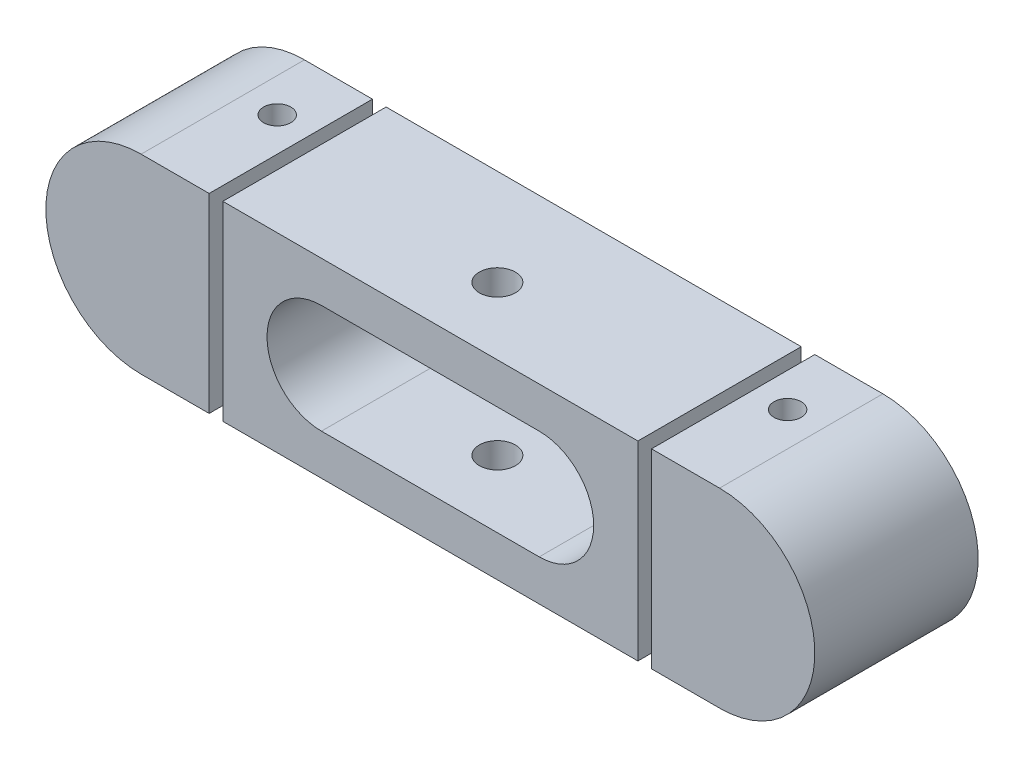
SolidWorks part; units mm, degrees
note: The reader was unsure of these and kept them because the rebuilt part matched: shared geometry of "草图2<3>".
ref_plane "前视基准面" through (0, 0, 0) normal (0, 0, 1) x (1, 0, 0)
ref_plane "上视基准面" through (0, 0, 0) normal (0, 1, 0) x (1, 0, 0)
ref_plane "右视基准面" through (0, 0, 0) normal (1, 0, 0) x (0, 0, -1)
other "Configuration Table"
sketch "草图2" plane through (0, 0, 0) normal (0, 0, 1) x (1, 0, 0)
  line L0 (-42.5, 36.6111) -> (-42.5, -23.6839) construction
  line L6 (-26.5, 0) -> (-58.5, 0) construction
  line L7 (-26.5, -8) -> (-58.5, -8)
  line L8 (-26.5, 8) -> (-58.5, 8)
  line L11 (-85, 0) -> (0, 0) construction
  line L12 (-85, 14) -> (0, 14)
  line L13 (-84.5, 3.05) -> (-84.5, -3.45)
  line L14 (-84.5, 3.05) -> (-84.5, 3.25)
  line L15 (-85, -14) -> (0, -14)
  line L16 (-84.5, 3.25) -> (-75.4817, 3.25)
  line L18 (-84.5, -3.45) -> (-75.4817, -3.45)
  line L26 (-75.4817, -3.45) -> (-75.3, -3.45)
  line L28 (-75.3, -3.45) -> (-75.3, 3.25)
  line L29 (-75.3, 3.25) -> (-75.4817, 3.25)
  line L30 (-9.7, 3.25) -> (-9.5183, 3.25)
  line L31 (-9.7, -3.45) -> (-9.7, 3.25)
  line L32 (-9.5183, -3.45) -> (-9.7, -3.45)
  line L33 (-0.5, -3.45) -> (-9.5183, -3.45)
  line L34 (-0.5, 3.25) -> (-9.5183, 3.25)
  line L35 (-0.5, 3.05) -> (-0.5, 3.25)
  line L36 (-0.5, 3.05) -> (-0.5, -3.45)
  arc A2 (-26.5, -8) -> (-26.5, 8) centre (-26.5, 0) ccw
  arc A3 (-58.5, 8) -> (-58.5, -8) centre (-58.5, 0) ccw
  arc A4 (-85, 14) -> (-85, -14) centre (-85, 0) ccw
  arc A5 (0, -14) -> (0, 14) centre (0, 0) ccw
  point P17 (-42.5, 0)
  point P40 (-42.5, 0)
  dimension "D4" = 8
  dimension "D1" = 85
  dimension "D2" = 42.5
  dimension "D3" = 32
  dimension "D5" = 32.8
  dimension "D8" = 28
  dimension "D9" = 32.8
extrude "凸台-拉伸1" add sketch "草图2" against normal blind 14
extrude "凸台-拉伸2" add sketch "草图2<3>" along normal blind 10
sketch "草图2<3>" plane through (0, 0, 0) normal (0, 0, 1) x (1, 0, 0) same geometry as "草图2"
sketch "草图3" plane through (0, 14, 0) normal (0, 1, 0) x (1, 0, 0)
  line L0 (-42.5, 20.2069) -> (-42.5, -13.7239) construction
  line L2 (14, -10) -> (14, 14) construction
  circle A8 centre (-5, 5) radius 2
  circle A9 centre (-80, 5) radius 2
  dimension "D1" = 56.5
  dimension "D2" = 37.5
  dimension "D3" = 4
  dimension "D4" = 4
  dimension "D5" = 37.5
extrude "切除-拉伸1" cut sketch "草图3" against normal through all both
sketch "草图4" plane through (0, 14, 0) normal (0, 1, 0) x (1, 0, 0)
  line L0 (0, 14) -> (0, -10) construction
  line L1 (-85, -10) -> (0, -10) construction
  circle A0 centre (-42.5, -0.15) radius 2.65
  dimension "D1" = 42.5
  dimension "D2" = 5.3
  dimension "D3" = 9.85
extrude "切除-拉伸2" cut sketch "草图4" against normal through all
sketch "草图6" plane through (0, 14, 0) normal (0, 1, 0) x (1, 0, 0)
  line L0 (-10, 14) -> (-10, -10)
  line L1 (-85, 14) -> (0, 14) construction
  line L2 (-85, -10) -> (0, -10) construction
  line L3 (-10, -10) -> (-12, -10)
  line L4 (-12, -10) -> (-12, 14)
  line L5 (-12, 14) -> (-10, 14)
  line L6 (0, 14) -> (0, -10) construction
  dimension "D1" = 2
  dimension "D2" = 10
extrude "切除-拉伸3" cut sketch "草图6" against normal blind 2
mirror "镜向1" about plane through (0, 0, 0) normal (0, 1, 0) of "切除-拉伸3"
sketch "草图7" plane through (0, 14, 0) normal (0, 1, 0) x (1, 0, 0)
  line L0 (-75, 14) -> (-75, -10)
  line L1 (-85, 14) -> (-12, 14) construction
  line L2 (-85, -10) -> (-12, -10) construction
  line L3 (-75, -10) -> (-73, -10)
  line L4 (-73, -10) -> (-73, 14)
  line L5 (-73, 14) -> (-75, 14)
  line L6 (-85, 14) -> (-85, -10) construction
  dimension "D1" = 2
  dimension "D2" = 10
extrude "切除-拉伸4" cut sketch "草图7" against normal blind 2
mirror "镜向2" about plane through (0, 0, 0) normal (0, 1, 0) of "切除-拉伸4"
sketch "草图8" plane through (0, 0, 10) normal (0, 0, 1) x (1, 0, 0)
  line L0 (-10, 14) -> (-10, -14)
  line L1 (-10, -14) -> (-12, -14)
  line L2 (-12, -14) -> (-12, 14)
  line L3 (-12, 14) -> (-10, 14)
  line L4 (-73, 14) -> (-75, 14)
  line L5 (-75, 14) -> (-75, -14)
  line L6 (-75, -14) -> (-73, -14)
  line L7 (-73, -14) -> (-73, 14)
extrude "切除-拉伸5" cut sketch "草图8" against normal blind 2
sketch "草图9" plane through (0, -14, 0) normal (0, -1, 0) x (1, 0, 0)
  line L0 (-75, -14) -> (-73, -14)
  line L1 (-73, -14) -> (-73, -13)
  line L2 (-73, 10) -> (-73, -14) construction
  line L3 (-73, -13) -> (-75, -13)
  line L4 (-75, -14) -> (-75, 10) construction
  line L5 (-75, -13) -> (-75, -14)
  line L6 (-12, -14) -> (-10, -14)
  line L7 (-10, -14) -> (-10, -13)
  line L8 (-10, 10) -> (-10, -14) construction
  line L9 (-10, -13) -> (-12, -13)
  line L10 (-12, -14) -> (-12, 10) construction
  line L11 (-12, -13) -> (-12, -14)
  dimension "D1" = 1
  dimension "D2" = 1
extrude "切除-拉伸6" cut sketch "草图9" against normal through all both and the other way through all
sketch "草图10" plane through (0, 0, 0) normal (0, 0, -1) x (-1, 0, 0)
  line L4 (84.5, 3.25) -> (75.3, 3.25)
  line L5 (75.3, 3.25) -> (75.3, -3.45)
  line L6 (75.3, -3.45) -> (84.5, -3.45)
  line L7 (84.5, -3.45) -> (84.5, 3.25)
  line L8 (84.5, 3.25) -> (75.3, 3.25)
  line L9 (75.3, 3.25) -> (75.3, -3.45)
  line L10 (75.3, -3.45) -> (84.5, -3.45)
  line L11 (84.5, -3.45) -> (84.5, 3.25)
  line L12 (0.5, 3.25) -> (0.5, -3.45)
  line L13 (0.5, -3.45) -> (9.7, -3.45)
  line L14 (9.7, -3.45) -> (9.7, 3.25)
  line L15 (9.7, 3.25) -> (0.5, 3.25)
  line L16 (0.5, 3.25) -> (0.5, -3.45)
  line L17 (0.5, -3.45) -> (9.7, -3.45)
  line L18 (9.7, -3.45) -> (9.7, 3.25)
  line L19 (9.7, 3.25) -> (0.5, 3.25)
  dimension "D1" = 0
  dimension "D2" = 0
extrude "切除-拉伸7" cut sketch "草图10" against normal blind 4
